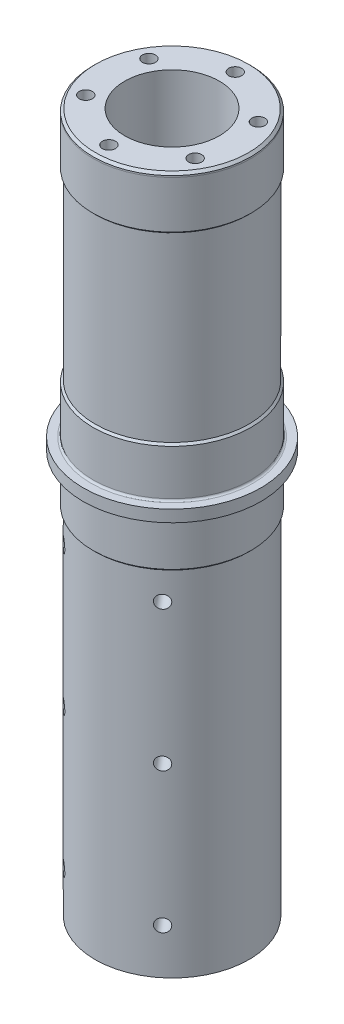
SolidWorks part; units mm, degrees
material "1.4305 (X8CrNiS18-9)"
ref_plane "Front Plane" through (0, 0, 0) normal (0, 0, 1) x (1, 0, 0)
ref_plane "Top Plane" through (0, 0, 0) normal (0, 1, 0) x (1, 0, 0)
ref_plane "Right Plane" through (0, 0, 0) normal (1, 0, 0) x (0, 0, -1)
ref_axis "Elbow" through (0, 145.8441, -30) along (0, -1, 0)
sketch "Sketch1" plane through (0, 0, 0) normal (1, 0, 0) x (0, 0, -1)
  line L0 (10, 58) -> (50, 58) construction
  line L1 (50, 129) -> (10, 129) construction
  line L2 (10, 58) -> (50, 58) construction
  line L3 (50, 129) -> (10, 129) construction
  line L4 (50, 130) -> (50, 117)
  line L6 (49.5, 42.5) -> (49.5, -47)
  line L7 (49.5, -47) -> (40.5, -47)
  line L8 (50, 130) -> (42, 130)
  line L9 (52.5, 58) -> (52.5, 55)
  line L11 (42, 130) -> (42, 62.5)
  line L12 (30, 145.8441) -> (30, -54.5) construction
  line L13 (50, 58) -> (52.5, 58)
  line L15 (50, 42.5) -> (49.5, 42.5)
  line L17 (50, 55) -> (50, 42.5)
  line L18 (42, 62.5) -> (40.5, 62.5)
  line L19 (40.5, 62.5) -> (40.5, -47)
  line L20 (40.5, -47) -> (42, -47) construction
  line L21 (42, 62.5) -> (42, -47) construction
  line L24 (52.5, 55) -> (50, 55)
  line L25 (50, 117) -> (10, 117) construction
  line L26 (10, 70) -> (50, 70) construction
  line L27 (50, 117) -> (10, 117) construction
  line L28 (10, 70) -> (50, 70) construction
  line L29 (50, 70) -> (50, 58)
  line L30 (50, 117) -> (49.5, 117)
  line L31 (49.5, 117) -> (49.5, 70)
  line L32 (49.5, 70) -> (50, 70)
  dimension "D1" = 2.5
  dimension "D2" = 1
  dimension "D3" = 105
  dimension "D4" = 177
  dimension "D5" = 8
  dimension "D6" = 12.5
  dimension "D7" = 0.5
  dimension "D8" = 20
  dimension "D9" = 0.5
  dimension "D11" = 9
  dimension "D12" = 20
  dimension "D13" = 3
revolve "Revolve1" add sketch "Sketch1" angle 360 about axis through (0, 145.8441, -30) along (0, -1, 0)
sketch "Sketch2" plane through (0, 0, 0) normal (1, 0, 0) x (0, 0, -1)
  line L0 (50, 129) -> (10, 129) construction
  line L1 (50, 129) -> (10, 129) construction
  line L4 (42, 133.5) -> (52.5, 133.5)
  line L5 (52.5, 133.5) -> (52.5, 129)
  line L6 (52.5, 129) -> (50, 129)
  line L7 (50, 129) -> (50, 130.5)
  line L8 (50, 130.5) -> (42, 130.5)
  line L9 (42, 133.5) -> (42, 130.5)
  line L10 (50, 117) -> (50, 130) construction
  line L11 (50, 130) -> (10, 130) construction
  dimension "D1" = 8
  dimension "D2" = 3
  dimension "D3" = 2.5
  dimension "D4" = 0.5
revolve "Revolve2" add sketch "Sketch2" angle 360 about axis through (0, 145.8441, -30) along (0, -1, 0)
sketch "Sketch8" plane through (0, 133.5, 0) normal (0, 1, 0) x (1, 0, 0)
  line L0 (0, 50) -> (0, 42) construction
  line L1 (0, 30) -> (0, 46) construction
  circle A0 centre (0, 30) radius 20 construction
  circle A1 centre (0, 30) radius 12 construction
  circle A2 centre (0, 30) radius 20 construction
  circle A3 centre (0, 30) radius 12 construction
  point P17 (0, 46)
  point P24 (13.8564, 38)
  point P25 (13.8564, 22)
  point P26 (0, 14)
  point P27 (-13.8564, 22)
  point P28 (-13.8564, 38)
  dimension "D1" = 6
hole_wizard "M4 Clearance Hole2" positions "Sketch8" profile "Sketch6" hole size "M4" standard "DIN" end condition up to next
sketch "Sketch6" plane through (-13.8564, 133.5, -38) normal (1, 0, 0) x (0, 0, 1)
  line L0 (0, 0) -> (0, 180.5)
  line L1 (0, 180.5) -> (2.15, 180.5)
  line L2 (2.15, 180.5) -> (2.15, 0)
  line L5 (2.15, 0) -> (0, 0)
  line L11 (0, -6.35) -> (0, 107.95) construction
  dimension "Thru Hole Dia." = 4.3
  dimension "Thru Hole Depth" = 180.5
sketch "Sketch13" plane through (0, 130, 0) normal (0, 1, 0) x (1, 0, 0)
  point P0 (0, 46)
  point P3 (13.8564, 38)
  point P6 (13.8564, 22)
  point P9 (-13.8564, 38)
  point P12 (-13.8564, 22)
  point P15 (0, 14)
hole_wizard "M4 Tapped Hole1" positions "Sketch13" profile "Sketch12" tap size "M4" standard "DIN"
sketch "Sketch12" plane through (0, 130, -46) normal (1, 0, 0) x (0, 0, 1)
  line L0 (0, 0) -> (0, 12.4914)
  line L1 (0, 12.4914) -> (1.65, 11.5)
  line L2 (1.65, 11.5) -> (1.65, 0)
  line L5 (1.65, 0) -> (0, 0)
  line L10 (0, 12.4914) -> (-1.65, 11.5) construction
  line L11 (0, -6.35) -> (0, 107.95) construction
  dimension "Tap Drill Dia." = 3.3
  dimension "Tap Drill Depth" = 11.5
  dimension "Drill Angle" = 118
cosmetic thread "Hole Thread1" parameters "D1"=8, "D2"=4
cosmetic thread "Hole Thread2" parameters "D1"=8, "D2"=4
cosmetic thread "Hole Thread3" parameters "D1"=8, "D2"=4
cosmetic thread "Hole Thread4" parameters "D1"=8, "D2"=4
cosmetic thread "Hole Thread5" parameters "D1"=8, "D2"=4
cosmetic thread "Hole Thread6" parameters "D1"=8, "D2"=4
sketch "Sketch14" plane through (0, 0, 0) normal (1, 0, 0) x (0, 0, -1)
  line L0 (50, 129) -> (10, 129) construction
  line L1 (10, 70) -> (50, 70) construction
  line L2 (50, 117) -> (10, 117) construction
  line L3 (50, 129) -> (10, 129)
  line L4 (10, 70) -> (50, 70)
  line L5 (50, 117) -> (10, 117)
split line "Split Line1"
hole_wizard "M4 Tapped Hole2" positions "3DSketch1" profile "Sketch16" tap size "M4" standard "DIN" end condition up to next
sketch3d "3DSketch1"
  circle A0 centre (-12.5344, 35.5, -15.0621) radius 2.15 construction
  circle A1 centre (-12.5344, 0, -15.0621) radius 2.15 construction
  circle A2 centre (-12.5344, -35.5, -15.0621) radius 2.15 construction
  circle A3 centre (12.5344, -35.5, -15.0621) radius 2.15 construction
  circle A4 centre (12.5344, 0, -15.0621) radius 2.15 construction
  circle A5 centre (12.5344, 35.5, -15.0621) radius 2.15 construction
  point P108 (12.5344, 35.5, -15.0621)
  point P110 (12.5344, 0, -15.0621)
  point P112 (12.5344, -35.5, -15.0621)
  point P114 (-12.5344, -35.5, -15.0621)
  point P116 (-12.5344, 0, -15.0621)
  point P118 (-12.5344, 35.5, -15.0621)
  point P124 (-11.1524, 35.5, -16.7091)
  point P127 (-11.1524, 0, -16.7091)
  point P132 (-11.1524, -35.5, -16.7091)
  point P135 (11.1524, -35.5, -16.7091)
  point P139 (11.1524, 0, -16.7091)
  point P142 (11.1524, 35.5, -16.7091)
cosmetic thread "Hole Thread7" parameters "D2"=4
cosmetic thread "Hole Thread9" parameters "D2"=4
cosmetic thread "Hole Thread12" parameters "D2"=4
cosmetic thread "Hole Thread13" parameters "D2"=4
cosmetic thread "Hole Thread25" parameters "D2"=4
cosmetic thread "Hole Thread27" parameters "D2"=4
sketch "Sketch16" plane through (12.5344, 35.5, -15.0621) normal (0, 1, 0) x (0.766, 0, -0.6428)
  line L0 (0, 0) -> (0, 19.5)
  line L1 (0, 19.5) -> (1.65, 19.5)
  line L2 (1.65, 19.5) -> (1.65, 0)
  line L5 (1.65, 0) -> (0, 0)
  line L11 (0, -6.35) -> (0, 107.95) construction
  dimension "Thru Tap Drill Dia." = 3.3
  dimension "Thru Tap Drill Depth" = 19.5
chamfer "Chamfer1" distance 0.6 angle 45 1 edges at (0, 130, -10)
fillet "Fillet1" radius 0.5 2 edges at (0, 55, -10) (0, 58, -10)
fillet "Fillet2" radius 0.4 1 edges at (0, 130.5, -10)
chamfer "Chamfer2" distance 0.5 angle 45 3 edges at (0, 70, -10.5) (0, 117, -10.5) (0, 42.5, -10)
delete or keep bodies "Body-Delete/Keep 1" type delete bodies bodies 103
delete or keep bodies "Body-Delete/Keep 2" [suppressed] type delete bodies bodies 108
